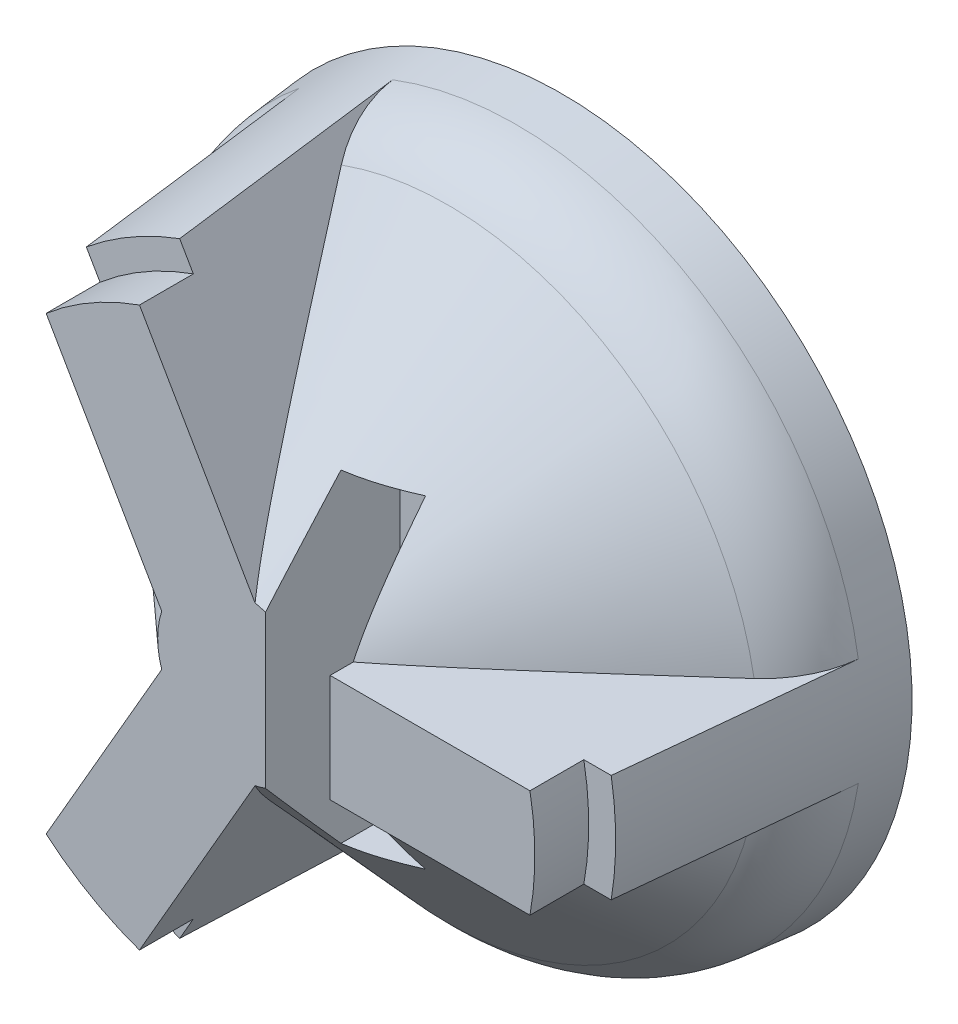
SolidWorks part; units mm, degrees
ref_plane "Plan de face" through (0, 0, 0) normal (0, 0, 1) x (1, 0, 0)
ref_plane "Plan de dessus" through (0, 0, 0) normal (0, 1, 0) x (1, 0, 0)
ref_plane "Plan de droite" through (0, 0, 0) normal (1, 0, 0) x (0, 0, -1)
sketch "Esquisse1" plane through (0, 0, 0) normal (0, 0, 1) x (1, 0, 0)
  line L0 (0, 0) -> (14, 0) construction
  line L1 (0, 0) -> (-7, 12.1244) construction
  line L2 (0, 0) -> (-7, -12.1244) construction
  line L3 (13.8564, 2) -> (2.2361, 2)
  line L4 (13.8564, -2) -> (2.2361, -2)
  line L5 (-5.1962, -13) -> (0.614, -2.9365)
  line L6 (-8.6603, -11) -> (-2.8501, -0.9365)
  line L7 (-8.6603, 11) -> (-2.8501, 0.9365)
  line L8 (-5.1962, 13) -> (0.614, 2.9365)
  circle A0 centre (0, 0) radius 14 construction
  circle A1 centre (0, 0) radius 3 construction
  circle A2 centre (0, 0) radius 3 construction
  arc A3 (13.8564, 2) -> (13.8564, -2) centre (0, 0) cw
  arc A4 (2.2361, -2) -> (1.5, -2.5981) centre (0, 0) cw
  arc A5 (2.2361, 2) -> (1.5, 2.5981) centre (0, 0) ccw
  arc A6 (0.614, -2.9365) -> (1.5, -2.5981) centre (0, 0) ccw
  arc A7 (-5.1962, -13) -> (-8.6603, -11) centre (0, 0) cw
  arc A8 (-2.8501, -0.9365) -> (-3, 0) centre (0, 0) cw
  arc A9 (-2.8501, 0.9365) -> (-3, 0) centre (0, 0) ccw
  arc A10 (-8.6603, 11) -> (-5.1962, 13) centre (0, 0) cw
  arc A11 (0.614, 2.9365) -> (1.5, 2.5981) centre (0, 0) cw
  point P30 (0, 0)
  dimension "D1" = 28
  dimension "D2" = 6
  dimension "D3" = 6
  dimension "D4" = 120
  dimension "D5" = 4
  dimension "D6" = 3
extrude "Boss.-Extru.1" add sketch "Esquisse1" along normal blind 12 contours A11 L8 A10 L7 A9 A8 L6 A7 L5 A6 A4 L4 A3 L3 A5 region at (0, 0, 0)
sketch "Esquisse4" plane through (0, 0, 0) normal (0, 1, 0) x (1, 0, 0)
  line L0 (14, 0) -> (3, -12) construction
  line L1 (3, -12) -> (0, -12)
  line L2 (0.614, -12) -> (2.2361, -12) construction
  line L3 (0, -12) -> (0, 0)
  line L4 (0, 0) -> (14, 0) construction
  line L5 (14, 0) -> (13.8564, 0) construction
  line L6 (13.8564, -12) -> (2.2361, -12) construction
  line L9 (14, -12) -> (14, 0) construction
  line L10 (14, -2) -> (14, 0)
  line L11 (14, 0) -> (0, 0)
  line L12 (3, -12) -> (14, -2)
  dimension "D1" = 2
  dimension "3" = 3
revolve "Révolution1" add sketch "Esquisse4" angle 360 about L3
sketch "Esquisse5" plane through (0, 0, 0) normal (0, 0, -1) x (-1, 0, 0)
  circle A0 centre (0, 0) radius 12.2
  dimension "D1" = 24.4
extrude "Enlèv. mat.-Extru.1" cut sketch "Esquisse5" against normal blind 2.5
sketch "Esquisse6" plane through (0, 0, 0) normal (0, 1, 0) x (1, 0, 0)
  line L0 (13, 0) -> (15.4808, 0)
  line L2 (15.4808, 0) -> (15.4808, -12)
  line L3 (15.4808, -12) -> (11.8, -12)
  line L4 (11.8, -12) -> (13, 0) construction
  line L6 (0, 0) -> (0, -11.8612) construction
  line L8 (13.8564, -12) -> (2.2361, -12) construction
  line L9 (13.8564, -12) -> (2.2361, -12) construction
  line L10 (13, 0) -> (12, -10)
  line L11 (12, -10) -> (11, -10)
  line L12 (11, -10) -> (11, -12)
  line L13 (11, -12) -> (11.8, -12)
  line L14 (14, -12) -> (14, 0) construction
  line L15 (14, 0) -> (-14, 0) construction
  point P2 (13, 0)
  point P13 (0, -11.8612)
  dimension "D1" = 1
  dimension "D2" = 1
  dimension "D3" = 2
  dimension "D4" = 11
revolve "Enlèvement de matière-Révolution1" cut sketch "Esquisse6" angle 360 about L6
fillet "Congé2" radius 4 3 edges at (6.34, -10.9812, 3.2) (-12.68, 0, 3.2) (6.34, 10.9812, 3.2)
sketch "Esquisse7" plane through (0, 0, 12) normal (0, 0, 1) x (1, 0, 0)
  line L0 (1, 6) -> (3.4, 6)
  line L1 (3.4, 6) -> (3.4, -6)
  line L2 (3.4, -6) -> (1, -6)
  line L3 (1, -6) -> (1, 6)
  line L4 (0, 0) -> (11, 0) construction
  arc A2 (10.8167, -2) -> (10.8167, 2) centre (0, 0) ccw construction
  dimension "D1" = 12
  dimension "D2" = 12
  dimension "D3" = 2.4
  dimension "D4" = 1
extrude "Enlèv. mat.-Extru.2" cut sketch "Esquisse7" against normal blind 5
